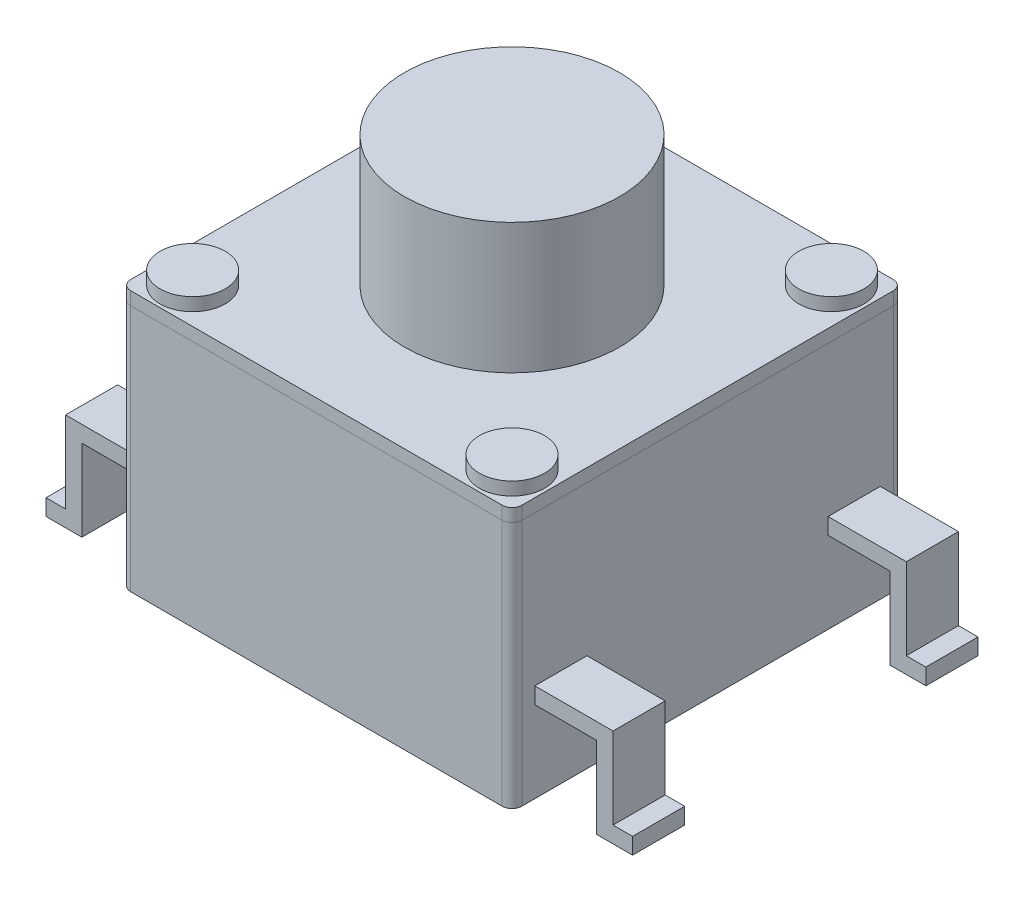
SolidWorks part; units mm, degrees
ref_plane "Front Plane" through (0, 0, 0) normal (0, 0, 1) x (1, 0, 0)
ref_plane "Top Plane" through (0, 0, 0) normal (0, 1, 0) x (1, 0, 0)
ref_plane "Right Plane" through (0, 0, 0) normal (1, 0, 0) x (0, 0, -1)
sketch "Sketch1" plane through (0, 0, 0) normal (0, 1, 0) x (1, 0, 0)
  line L0 (3, 8.1371) -> (3, -3.3089) construction
  line L1 (0, 0) -> (6, 0)
  line L2 (0, 0) -> (0, 6)
  line L3 (0, 6) -> (6, 6)
  line L4 (6, 0) -> (6, 6)
  line L5 (-2.1426, 3) -> (8.6394, 3) construction
  circle A0 centre (3, 3) radius 1.65
  circle A1 centre (0.55, 5.45) radius 0.5
  circle A2 centre (5.45, 5.45) radius 0.5
  circle A3 centre (5.45, 0.55) radius 0.5
  circle A4 centre (0.55, 0.55) radius 0.5
  dimension "D3" = 3.3
  dimension "D4" = 1
  dimension "D1" = 6
  dimension "D2" = 6
  dimension "D5" = 0.55
  dimension "D6" = 0.55
  dimension "D7" = 3
  dimension "D8" = 3
extrude "Boss-Extrude1" add sketch "Sketch1" along normal blind 3.8 contours L1 L4 L3 L2
extrude "Boss-Extrude2" add sketch "Sketch1<3>" along normal blind 6 contours A0
sketch "Sketch1<3>" plane through (0, 0, 0) normal (0, 1, 0) x (1, 0, 0) same geometry as "Sketch1"
extrude "Boss-Extrude3" add sketch "Sketch1<4>" along normal blind 4.2 contours A1 | A4 | A3 | A2
sketch "Sketch1<4>" plane through (0, 0, 0) normal (0, 1, 0) x (1, 0, 0) same geometry as "Sketch1"
sketch "Sketch2" plane through (0, 3.8, 0) normal (0, 1, 0) x (1, 0, 0)
  line L4 (0, 6) -> (0, 0)
  line L5 (0, 0) -> (6, 0)
  line L6 (6, 0) -> (6, 6)
  line L7 (6, 6) -> (0, 6)
  line L8 (0, 6) -> (0, 0)
  line L9 (0, 0) -> (6, 0)
  line L10 (6, 0) -> (6, 6)
  line L11 (6, 6) -> (0, 6)
  circle A0 centre (3, 3) radius 1.65 construction
  circle A1 centre (3, 3) radius 1.65
  circle A2 centre (5.45, 0.55) radius 0.5 construction
  circle A3 centre (0.55, 0.55) radius 0.5 construction
  circle A4 centre (0.55, 5.45) radius 0.5 construction
  circle A5 centre (5.45, 5.45) radius 0.5 construction
  circle A6 centre (5.45, 0.55) radius 0.5
  circle A7 centre (0.55, 0.55) radius 0.5
  circle A8 centre (0.55, 5.45) radius 0.5
  circle A9 centre (5.45, 5.45) radius 0.5
  dimension "D1" = 0
extrude "Boss-Extrude4" add sketch "Sketch2" along normal blind 0.2 separate body
fillet "Fillet1" radius 0.15 4 edges at (0, 1.9, 0) (0, 1.9, -6) (6, 1.9, -6) (6, 1.9, 0)
fillet "Fillet2" radius 0.15 4 edges at (6, 3.9, -6) (6, 3.9, 0) (0, 3.9, 0) (0, 3.9, -6)
sketch "Sketch3" plane through (0, 0, -6) normal (0, 0, -1) x (-1, 0, 0)
  line L0 (-6, 0) -> (-6, 3.8) construction
  line L1 (-6, 1.25) -> (-6.95, 1.25)
  line L2 (-6, 1.25) -> (-6, 1.5)
  line L3 (-6, 1.5) -> (-7.2, 1.5)
  line L5 (-0.15, 0) -> (-5.85, 0) construction
  line L7 (-7.2, 1.5) -> (-7.2, 0.25)
  line L9 (-6.95, 1.25) -> (-6.95, 0)
  line L10 (-6.95, 0) -> (-7.5, 0)
  line L12 (-7.2, 0.25) -> (-7.5, 0.25)
  line L13 (-7.5, 0) -> (-7.5, 0.25)
  dimension "D1" = 1.5
  dimension "D2" = 0.25
  dimension "D3" = 0.25
  dimension "D4" = 0.25
  dimension "D5" = 1.2
  dimension "D6" = 1.5
extrude "Boss-Extrude5" add sketch "Sketch3" along normal blind 0.4 and the other way blind 0.4 from offset 0.75 offset against normal yes
extrude "Boss-Extrude6" add sketch "Sketch3<2>" along normal blind 0.4 and the other way blind 0.4 from offset 5.25 contours L9 L10 L13 L12 L7 L3 L2 L1 offset against normal yes
sketch "Sketch3<2>" plane through (0, 0, -6) normal (0, 0, -1) x (-1, 0, 0) same geometry as "Sketch3"
ref_plane "Plane1" through (3, 0, 0) normal (1, 0, 0) x (0, 0, -1)
mirror "Mirror1" about plane through (3, 0, 0) normal (1, 0, 0) of "Boss-Extrude5", "Boss-Extrude6"
